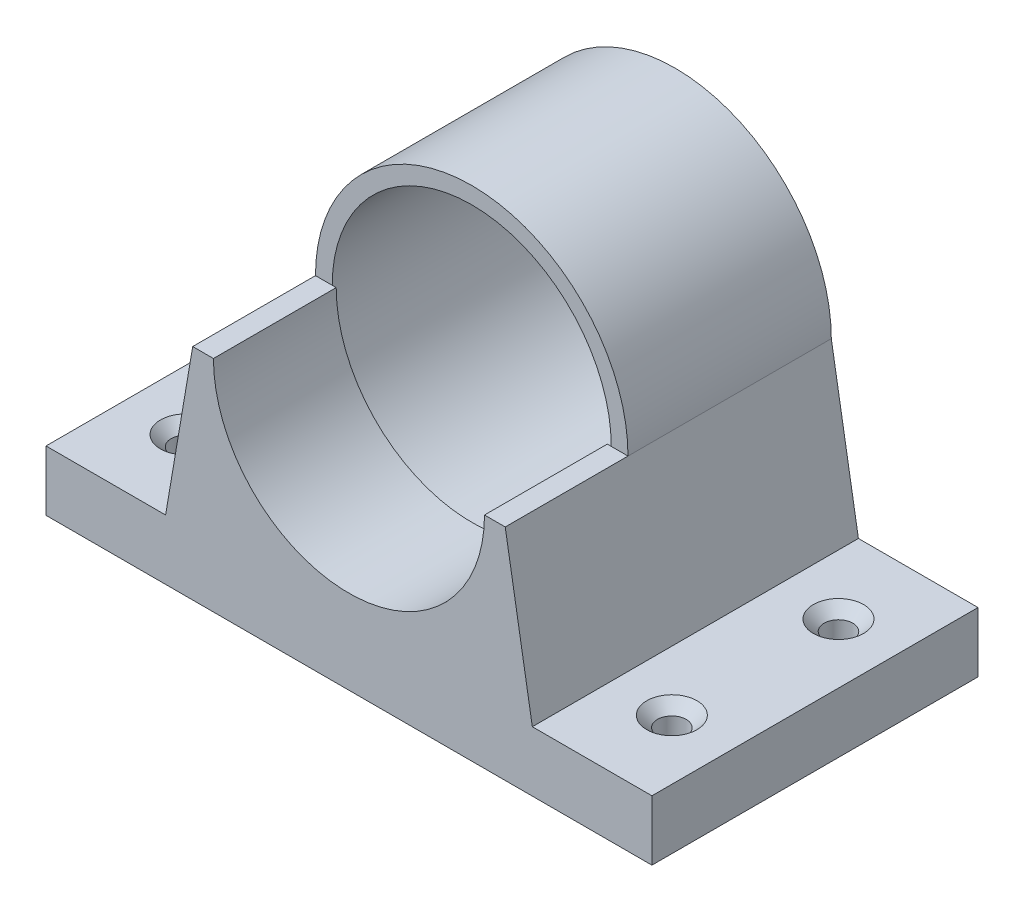
SolidWorks part; units mm, degrees
note: The reader was unsure of these and kept them because the rebuilt part matched: shared geometry of "Sketch1<15>", "Sketch1<19>".
ref_plane "Front Plane" through (0, 0, 0) normal (0, 0, 1) x (1, 0, 0)
ref_plane "Top Plane" through (0, 0, 0) normal (0, 1, 0) x (1, 0, 0)
ref_plane "Right Plane" through (0, 0, 0) normal (1, 0, 0) x (0, 0, -1)
sketch "Sketch1" plane through (0, 0, 0) normal (0, 0, 1) x (1, 0, 0)
  line L0 (-23, -1.8466) -> (-38, -1.8466)
  line L6 (-38, -1.8466) -> (-38, -6.8466)
  line L7 (23, -1.8466) -> (38, -1.8466)
  line L9 (0, 0) -> (0, 18.1534)
  line L12 (38, -1.8466) -> (38, -6.8466)
  line L13 (-23, -1.8466) -> (-19.6, 18.1534)
  line L14 (19.6, 18.1534) -> (23, -1.8466)
  line L15 (-38, -6.8466) -> (38, -6.8466)
  line L16 (-19.6, 18.1534) -> (-17, 18.1534)
  line L17 (17, 18.1534) -> (19.6, 18.1534)
  circle A2 centre (0, 18.1534) radius 17.5
  arc A3 (-19.6, 18.1534) -> (19.6, 18.1534) centre (0, 18.1534) cw
  arc A4 (-19.6, 18.1534) -> (19.6, 18.1534) centre (0, 18.1534) ccw
  arc A6 (17, 18.1534) -> (-17, 18.1534) centre (0, 18.1534) cw
  dimension "D3" = 35
  dimension "D4" = 17
  dimension "D5" = 19.6
  dimension "D1" = 25
  dimension "D2" = 5
  dimension "D7" = 15
  dimension "D8" = 23
extrude "Boss-Extrude9" add sketch "Sketch1" against normal blind 25.5 contours A3 A4 | A2
extrude "Boss-Extrude10" add sketch "Sketch1<15>" against normal blind 25.5 and the other way blind 15.4 contours L13 L0 L6 L15 L12 L7 L14 A4
sketch "Sketch1<15>" plane through (0, 0, 0) normal (0, 0, 1) x (1, 0, 0) same geometry as "Sketch1"
sketch "Sketch8" plane through (0, -1.8466, 0) normal (0, 1, 0) x (1, 0, 0)
  line L0 (-30.5, -15.4) -> (-30.5, -5.4)
  line L1 (-23, -15.4) -> (-38, -15.4) construction
  line L2 (-23, 25.5) -> (-38, 25.5) construction
  line L3 (-30.5, 25.5) -> (-30.5, 15.5)
  line L4 (0, 0) -> (0, 27.9846) construction
  line L5 (30.5, -15.4) -> (30.5, -5.4)
  line L6 (30.5, 25.5) -> (30.5, 15.5)
  dimension "D1" = 10
hole_wizard "CSK for M3 Flat Head Machine Screw1" positions "Sketch11" profile "Sketch10" countersink size "M3" standard "ANSI Metric" end condition through all
sketch "Sketch11" plane through (0, -1.8466, 0) normal (0, 1, 0) x (1, 0, 0)
  point P0 (-30.5, 15.5)
  point P3 (-30.5, -5.4)
sketch "Sketch10" plane through (-30.5, -1.8466, -15.5) normal (1, 0, 0) x (0, 0, 1)
  line L0 (0, 0) -> (0, 5)
  line L1 (0, 5) -> (1.8, 5)
  line L2 (1.8, 5) -> (1.8, 1.35)
  line L3 (1.8, 1.35) -> (3.15, 0)
  line L5 (3.15, 0) -> (0, 0)
  line L6 (-1.8, 1.35) -> (-3.15, 0) construction
  line L11 (0, -6.35) -> (0, 107.95) construction
  dimension "Thru Hole Dia." = 3.6
  dimension "Thru Hole Depth" = 5
  dimension "Near C'Sink Dia." = 6.3
  dimension "Near C'Sink Angle" = 90
hole_wizard "CSK for M3 Flat Head Machine Screw2" positions "Sketch13" profile "Sketch14" countersink size "M3" standard "ANSI Metric" end condition through all
sketch "Sketch13" plane through (0, -1.8466, 0) normal (0, 1, 0) x (1, 0, 0)
  point P0 (30.5, -5.4)
  point P3 (30.5, 15.5)
sketch "Sketch14" plane through (30.5, -1.8466, 5.4) normal (1, 0, 0) x (0, 0, 1)
  line L0 (0, 0) -> (0, 5)
  line L1 (0, 5) -> (1.8, 5)
  line L2 (1.8, 5) -> (1.8, 1.35)
  line L3 (1.8, 1.35) -> (3.15, 0)
  line L5 (3.15, 0) -> (0, 0)
  line L6 (-1.8, 1.35) -> (-3.15, 0) construction
  line L11 (0, -6.35) -> (0, 107.95) construction
  dimension "Thru Hole Dia." = 3.6
  dimension "Thru Hole Depth" = 5
  dimension "Near C'Sink Dia." = 6.3
  dimension "Near C'Sink Angle" = 90
extrude "Boss-Extrude11" add sketch "Sketch1<19>" along normal blind 15.4
sketch "Sketch1<19>" plane through (0, 0, 0) normal (0, 0, 1) x (1, 0, 0) same geometry as "Sketch1"
extrude "Cut-Extrude3" cut sketch "Sketch17" against normal up to surface (4.826 mm away)
sketch "Sketch17" plane through (-499.2489, 9.9746, -84.3089) normal (0.0361, 0.9993, -0.0009) x (0.0508, -0.0009, 0.9987)
  circle A0 centre (67.5, 464.5) radius 1.7
  circle A2 centre (92.5, 462.5) radius 1.8
  circle A3 centre (113.4, 462.5) radius 1.8
  circle A4 centre (92.5, 401.5) radius 1.8
  circle A5 centre (113.4, 401.5) radius 1.8
  circle A7 centre (67.5, 399.5) radius 1.7
  circle A8 centre (44.5, 399.5) radius 1.7
  circle A9 centre (33.5, 468.8378) radius 1.7
  circle A10 centre (33.5, 435.8378) radius 1.7
  circle A11 centre (44.5, 464.5) radius 1.7
sketch "Sketch18" plane through (0, -6.8466, 0) normal (0, -1, 0) x (1, 0, 0)
  line L1 (-38, 15.4) -> (38, 15.4)
  line L2 (-38, 15.4) -> (-38, -25.5)
  line L3 (-38, -25.5) -> (38, -25.5)
  line L4 (38, 15.4) -> (38, -25.5)
extrude "Boss-Extrude12" add sketch "Sketch18" along normal blind 2.54
